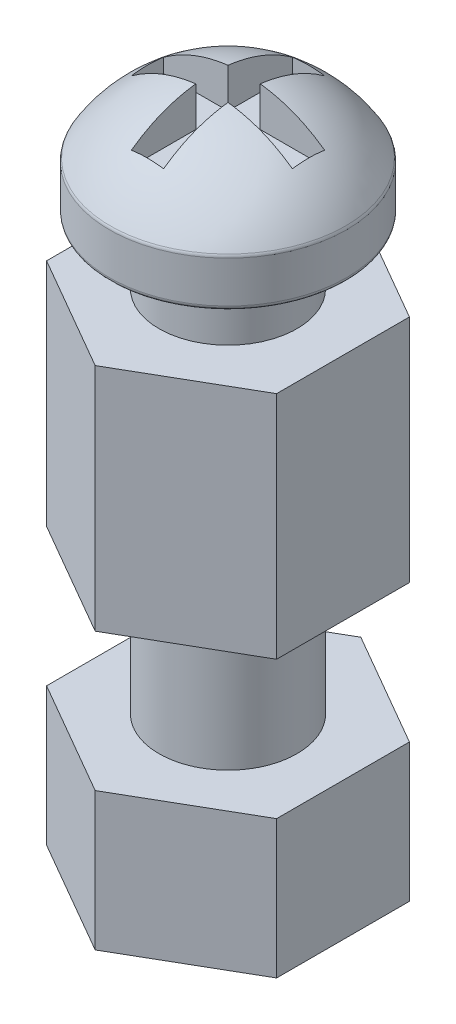
SolidWorks part; units mm, degrees
ref_plane "Front Plane" through (0, 0, 0) normal (0, 0, 1) x (1, 0, 0)
ref_plane "Top Plane" through (0, 0, 0) normal (0, 1, 0) x (1, 0, 0)
ref_plane "Right Plane" through (0, 0, 0) normal (1, 0, 0) x (0, 0, -1)
sketch "Sketch1" plane through (0, 0, 0) normal (0, 1, 0) x (1, 0, 0)
  line L1 (2.5, 1.4434) -> (0, 2.8868)
  line L2 (0, 2.8868) -> (-2.5, 1.4434)
  line L3 (-2.5, 1.4434) -> (-2.5, -1.4434)
  line L4 (-2.5, -1.4434) -> (0, -2.8868)
  line L5 (0, -2.8868) -> (2.5, -1.4434)
  line L6 (2.5, -1.4434) -> (2.5, 1.4434)
  circle A0 centre (0, 0) radius 2.5 construction
  circle A1 centre (0, 0) radius 1.5
  point P10 (0, 2.6144)
  dimension "D1" = 3
  dimension "D2" = 5
extrude "Boss-Extrude1" add sketch "Sketch1" along normal blind 5 contours A1 | L5 L6 L1 L2 L3 L4 A1 region at (2.4236, 0, 0) region at (0, 0, 0)
extrude "Boss-Extrude2" add sketch "Sketch1<4>" against normal blind 6 contours A1 region at (0, 0, 0)
sketch "Sketch1<4>" plane through (0, 0, 0) normal (0, 1, 0) x (1, 0, 0) same geometry as "Sketch1"
sketch "Sketch3" plane through (0, 0, 0) normal (0, 0, 1) x (1, 0, 0)
  line L0 (1.5, -6) -> (1.5, 0) construction
  line L1 (0, 5) -> (1.5, 5)
  line L2 (0, 5) -> (0, 6.4)
  line L3 (0, 6.4) -> (1.5, 6.4)
  line L4 (1.5, 5) -> (1.5, 6.4)
  line L5 (0, 5) -> (0, 0) construction
  line L6 (1.5, 6.4) -> (3.6588, 6.4)
  line L7 (0, 6.4) -> (0, 8.9)
  line L8 (0, 5) -> (0, -6) construction
  line L9 (-1.5, -6) -> (1.5, -6) construction
  line L10 (0, -0.5) -> (3.9182, -0.5) construction
  line L11 (0, -7.4) -> (0, -9.9)
  line L12 (1.5, -7.4) -> (3.6588, -7.4)
  line L13 (1.5, -6) -> (1.5, -7.4)
  line L14 (0, -7.4) -> (1.5, -7.4)
  line L15 (0, -6) -> (0, -7.4)
  line L16 (0, -6) -> (1.5, -6)
  line L17 (2.5777, 7.4) -> (2.5777, 6.4)
  circle A0 centre (0, 5.9) radius 3
  circle A1 centre (2.4527, 7.4) radius 0.125
  circle A2 centre (0, -6.9) radius 3
  circle A3 centre (2.4527, -8.4) radius 0.125
  point P29 (0, 6.5303)
  point P30 (0, 6.863)
  dimension "D2" = 0.25
  dimension "D5" = 6
  dimension "D1" = 1.4
  dimension "D3" = 1
  dimension "D4" = 0.5
revolve "Revolve1" add sketch "Sketch3" angle 360 about L8 region at (0.75, 5.7, 0) region at (1.1363, 7.4777, 0) region at (2.4527, 7.4, 0)
ref_plane "Plane1" through (0, 15, 0) normal (0, 1, 0) x (1, 0, 0)
sketch "Sketch4" plane through (0, 15, 0) normal (0, 1, 0) x (1, 0, 0)
  line L1 (-1.75, -0.35) -> (1.75, -0.35)
  line L2 (-1.75, -0.35) -> (-1.75, 0.35)
  line L3 (-1.75, 0.35) -> (1.75, 0.35)
  line L4 (1.75, -0.35) -> (1.75, 0.35)
  line L5 (-1.75, -0.35) -> (1.75, 0.35) construction
  line L6 (-1.75, 0.35) -> (1.75, -0.35) construction
  line L7 (-0.35, -1.75) -> (0.35, -1.75)
  line L8 (-0.35, -1.75) -> (-0.35, 1.75)
  line L9 (-0.35, 1.75) -> (0.35, 1.75)
  line L10 (0.35, -1.75) -> (0.35, 1.75)
  line L11 (-0.35, -1.75) -> (0.35, 1.75) construction
  line L12 (-0.35, 1.75) -> (0.35, -1.75) construction
  point P0 (0, 0)
  point P6 (0, 0)
  dimension "D1" = 0.7
  dimension "D2" = 3.5
extrude "Cut-Extrude1" cut sketch "Sketch4" against normal blind 7 contours L7 L10 L1 L8 | L10 L1 L4 L3 | L3 L10 L9 L8 | L1 L8 L3 L2 | L1 L10 L3 L8 region at (-1.05, 15, 0) region at (0, 15, 0) region at (0, 15, 1.05) region at (1.05, 15, 0) region at (0, 15, -1.05)
fillet "Fillet1" radius 0.1 1 edges at (-2.5777, 6.4, 0)
sketch "Sketch5" plane through (0, -6, 0) normal (0, -1, 0) x (1, 0, 0)
  line L6 (2.5, 1.4434) -> (0, 2.8868)
  line L7 (0, 2.8868) -> (-2.5, 1.4434)
  line L8 (-2.5, 1.4434) -> (-2.5, -1.4434)
  line L9 (-2.5, -1.4434) -> (0, -2.8868)
  line L10 (0, -2.8868) -> (2.5, -1.4434)
  line L11 (2.5, -1.4434) -> (2.5, 1.4434)
  line L12 (2.5, 1.4434) -> (0, 2.8868)
  line L13 (0, 2.8868) -> (-2.5, 1.4434)
  line L14 (-2.5, 1.4434) -> (-2.5, -1.4434)
  line L15 (-2.5, -1.4434) -> (0, -2.8868)
  line L16 (0, -2.8868) -> (2.5, -1.4434)
  line L17 (2.5, -1.4434) -> (2.5, 1.4434)
  circle A0 centre (0, 0) radius 1.5 construction
  circle A1 centre (0, 0) radius 1.5
  dimension "D1" = 0
extrude "Boss-Extrude3" add sketch "Sketch5" against normal blind 3 separate body
